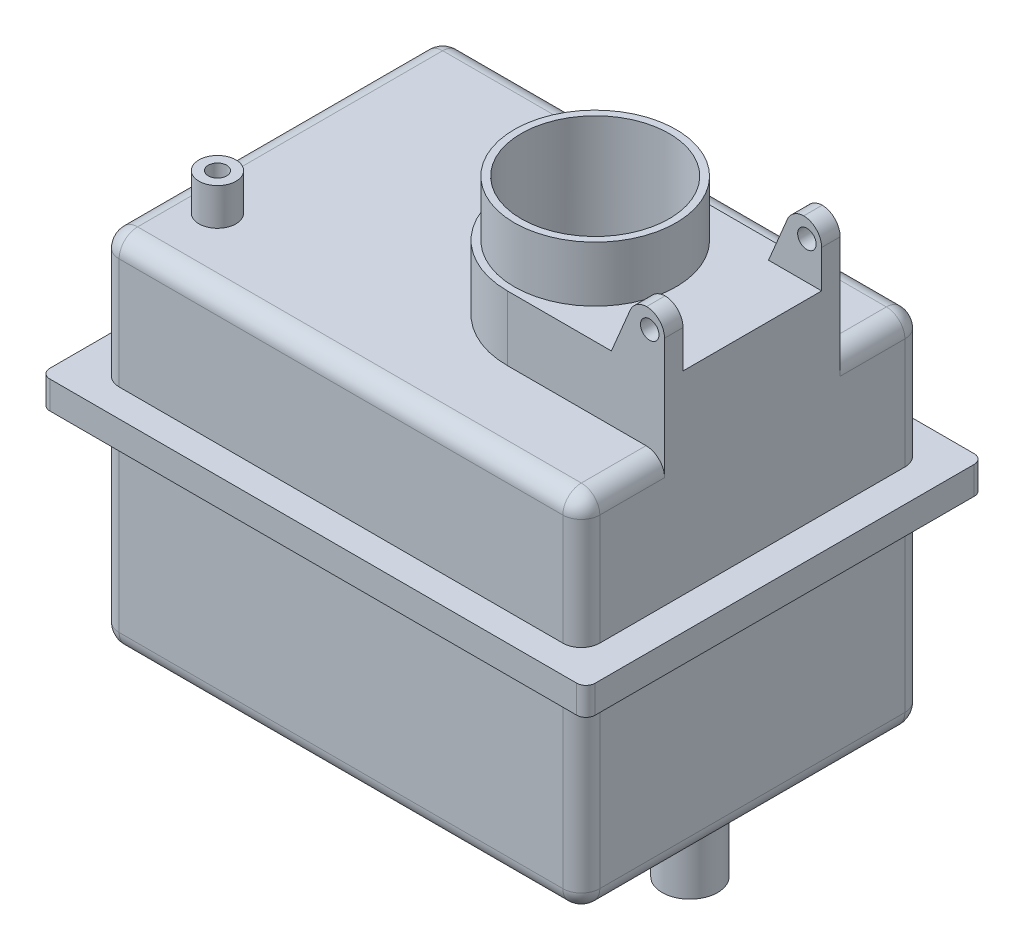
SolidWorks part; units mm, degrees
material "PBT General Purpose"
ref_plane "Front Plane" through (0, 0, 0) normal (0, 0, 1) x (1, 0, 0)
ref_plane "Top Plane" through (0, 0, 0) normal (0, 1, 0) x (1, 0, 0)
ref_plane "Right Plane" through (0, 0, 0) normal (1, 0, 0) x (0, 0, -1)
sketch "Sketch1" plane through (0, 0, 0) normal (0, 1, 0) x (1, 0, 0)
  line L1 (0, 0) -> (52, 0)
  line L2 (0, 0) -> (0, 37)
  line L3 (0, 37) -> (52, 37)
  line L4 (52, 0) -> (52, 37)
  dimension "D1" = 37
  dimension "D2" = 52
extrude "Boss-Extrude1" add sketch "Sketch1" along normal blind 22
sketch "Sketch2" plane through (0, 22, 0) normal (0, 1, 0) x (1, 0, 0)
  line L0 (26, 40) -> (26, 37) construction
  line L1 (-3.5, 40) -> (55.5, 40)
  line L2 (-3.5, 40) -> (-3.5, -3)
  line L3 (-3.5, -3) -> (55.5, -3)
  line L4 (55.5, 40) -> (55.5, -3)
  line L5 (-3.5, 40) -> (55.5, -3) construction
  line L6 (-3.5, -3) -> (55.5, 40) construction
  line L7 (52, 37) -> (0, 37) construction
  line L8 (26, 0) -> (26, -3) construction
  line L9 (0, 0) -> (52, 0) construction
  point P0 (26, 18.5)
  dimension "D1" = 59
  dimension "D2" = 43
extrude "Boss-Extrude2" add sketch "Sketch2" along normal blind 3
sketch "Sketch3" plane through (0, 25, 0) normal (0, 1, 0) x (1, 0, 0)
  line L0 (26, 37) -> (26, 40) construction
  line L1 (0, 37) -> (52, 37)
  line L2 (0, 37) -> (0, 0)
  line L3 (0, 0) -> (52, 0)
  line L4 (52, 37) -> (52, 0)
  line L5 (0, 37) -> (52, 0) construction
  line L6 (0, 0) -> (52, 37) construction
  line L7 (55.5, 40) -> (-3.5, 40) construction
  line L8 (26, 0) -> (26, -3) construction
  line L9 (-3.5, -3) -> (55.5, -3) construction
  point P0 (26, 18.5)
  dimension "D1" = 37
  dimension "D2" = 52
extrude "Boss-Extrude3" add sketch "Sketch3" along normal blind 12
sketch "Sketch4" plane through (0, 37, 0) normal (0, 1, 0) x (1, 0, 0)
  line L1 (1.3582, 35.9949) -> (50.6418, 35.9949)
  line L2 (1.3582, 35.9949) -> (1.3582, 1.0051)
  line L3 (1.3582, 1.0051) -> (50.6418, 1.0051)
  line L4 (50.6418, 35.9949) -> (50.6418, 1.0051)
  line L5 (1.3582, 35.9949) -> (50.6418, 1.0051) construction
  line L6 (1.3582, 1.0051) -> (50.6418, 35.9949) construction
  point P0 (26, 18.5)
extrude "Cut-Extrude1" cut sketch "Sketch4" against normal blind 36
sketch "Sketch5" plane through (0, 37, 0) normal (0, 1, 0) x (1, 0, 0)
  line L0 (52, 0) -> (52, 37) construction
  line L1 (0, 0) -> (52, 0)
  line L2 (0, 0) -> (0, 37)
  line L3 (0, 37) -> (52, 37)
  line L4 (52, 0) -> (52, 37)
extrude "Boss-Extrude4" add sketch "Sketch5" along normal blind 2
fillet "Fillet1" radius 2 8 edges at (0, 39, -18.5) (0, 32, -37) (26, 39, -37) (52, 32, -37) (52, 39, -18.5) (52, 32, 0) (0, 32, 0) (26, 39, 0)
fillet "Fillet2" radius 1 4 edges at (55.5, 23.5, 3) (55.5, 23.5, -40) (-3.5, 23.5, -40) (-3.5, 23.5, 3)
fillet "Fillet3" radius 2 8 edges at (52, 0, -18.5) (52, 11, -37) (26, 0, -37) (26, 0, 0) (0, 0, -18.5) (0, 11, -37) (0, 11, 0) (52, 11, 0)
sketch "Sketch6" plane through (0, 39, 0) normal (0, 1, 0) x (1, 0, 0)
  line L0 (50, 35) -> (50, 2) construction
  line L1 (52, 37) -> (52, 0) construction
  line L2 (52, 28) -> (52, 9)
  line L4 (52, 28) -> (35, 28)
  line L5 (52, 28) -> (52, 9)
  line L6 (52, 9) -> (35, 9)
  line L7 (35, 28) -> (35, 9)
  point P9 (52, 18.5)
  line M6 (50, 2) -> (50, 35)
  dimension "D1" = 19
  dimension "D2" = 17
extrude "Boss-Extrude5" add sketch "Sketch6" against normal blind 2 contours L6 L2 L4 M6 region at (51, 39, -18.5)
sketch "Sketch7" plane through (0, 39, 0) normal (0, 1, 0) x (1, 0, 0)
  line L1 (52, 9) -> (35, 9)
  line L2 (52, 9) -> (52, 28)
  line L3 (52, 28) -> (35, 28)
  line L4 (35, 9) -> (35, 28)
  dimension "D1" = 19
  dimension "D2" = 17
extrude "Boss-Extrude6" add sketch "Sketch7" along normal blind 7
sketch "Sketch8" plane through (0, 46, 0) normal (0, 1, 0) x (1, 0, 0)
  line L0 (35, 28) -> (35, 9) construction
  circle A0 centre (35, 18.5) radius 9.5
  circle A1 centre (35, 18.5) radius 8
  dimension "D1" = 19
  dimension "D2" = 16
extrude "Boss-Extrude7" add sketch "Sketch8" against normal blind 7
sketch "Sketch9" plane through (0, 46, 0) normal (0, 1, 0) x (1, 0, 0)
  line L0 (35, 26.5) -> (35, 10.5) construction
  circle A0 centre (35, 18.5) radius 8
  dimension "D1" = 16
extrude "Cut-Extrude2" cut sketch "Sketch9" against normal blind 10
sketch "Sketch10" plane through (0, 46, 0) normal (0, 1, 0) x (1, 0, 0)
  circle A0 centre (35, 18.5) radius 8.75
  circle A1 centre (35, 18.5) radius 8
  dimension "D1" = 17.5
  dimension "D2" = 16
extrude "Boss-Extrude8" add sketch "Sketch10" along normal blind 6
sketch "Sketch11" plane through (0, 0, -9) normal (0, 0, 1) x (1, 0, 0)
  line L0 (52, 46) -> (52, 52.068)
  line L1 (52, 52.068) -> (48.7989, 52.068)
  line L2 (48.7989, 52.068) -> (46.2515, 46)
  line L3 (35, 46) -> (52, 46) construction
  circle A0 centre (50.3994, 50.0726) radius 1
  line M3 (52, 46) -> (35, 46)
  dimension "D1" = 2
extrude "Boss-Extrude9" add sketch "Sketch11" against normal blind 2 contours L1 L2 L0 A0 M3 region at (49.611, 48.5726, -9)
sketch "Sketch12" plane through (0, 0, -28) normal (0, 0, -1) x (-1, 0, 0)
  line L0 (-52, 46) -> (-52, 52.068)
  line L1 (-52, 52.068) -> (-48.7989, 52.068)
  line L2 (-52, 52.068) -> (-48.7989, 52.068) construction
  line L3 (-48.7989, 52.068) -> (-46.2515, 46)
  circle A0 centre (-50.3994, 50.0726) radius 1
  line M5 (-35, 46) -> (-52, 46)
extrude "Boss-Extrude10" add sketch "Sketch12" against normal blind 2 contours L3 L1 L0 A0 M5 region at (49.611, 48.5726, -28)
fillet "Fillet4" radius 2 4 edges at (48.7989, 52.068, -27) (48.7989, 52.068, -10) (52, 52.068, -10) (52, 52.068, -27)
sketch "Sketch13" plane through (0, 39, 0) normal (0, 1, 0) x (1, 0, 0)
  circle A0 centre (5.0433, 7.5936) radius 2
  dimension "D1" = 4
extrude "Boss-Extrude11" add sketch "Sketch13" along normal blind 4
sketch "Sketch14" plane through (0, 43, 0) normal (0, 1, 0) x (1, 0, 0)
  circle A0 centre (5.0433, 7.5936) radius 1
  dimension "D1" = 2
extrude "Cut-Extrude3" cut sketch "Sketch14" against normal blind 16
sketch "Sketch15" plane through (0, 0, 0) normal (0, -1, 0) x (1, 0, 0)
  circle A0 centre (9.4357, -27.7314) radius 5
  dimension "D1" = 10
extrude "Boss-Extrude12" add sketch "Sketch15" along normal blind 6
sketch "Sketch16" plane through (0, -6, 0) normal (0, -1, 0) x (1, 0, 0)
  circle A0 centre (9.4357, -27.7314) radius 4.25
  dimension "D1" = 8.5
extrude "Cut-Extrude4" cut sketch "Sketch16" against normal blind 12
sketch "Sketch17" plane through (0, -6, 0) normal (0, -1, 0) x (1, 0, 0)
  circle A0 centre (9.4357, -27.7314) radius 5
extrude "Boss-Extrude13" add sketch "Sketch17" along normal blind 1
ref_plane "Plane1" through (4.4357, 0, 0) normal (-1, 0, 0) x (0, 0, 1)
sketch "Sketch18" plane through (4.4357, 0, 0) normal (-1, 0, 0) x (0, 0, 1)
  circle A0 centre (-27.8879, -4.2305) radius 2
  dimension "D1" = 4
extrude "Boss-Extrude14" add sketch "Sketch18" against normal blind 1
sketch "Sketch19" plane through (4.4357, 0, 0) normal (-1, 0, 0) x (0, 0, 1)
  circle A0 centre (-27.8879, -4.2305) radius 2
extrude "Boss-Extrude15" add sketch "Sketch19" along normal blind 5
sketch "Sketch20" plane through (-0.5643, 0, 0) normal (-1, 0, 0) x (0, 0, 1)
  circle A0 centre (-27.8879, -4.2305) radius 1
  dimension "D1" = 2
extrude "Cut-Extrude5" cut sketch "Sketch20" against normal blind 7
sketch "Sketch21" plane through (0, 0, 0) normal (0, -1, 0) x (1, 0, 0)
  line L0 (5.9367, -2) -> (5.9367, -35.1388) construction
  line L1 (50, -2) -> (2, -2) construction
  line L2 (45.2444, -2) -> (45.2444, -35) construction
  line L3 (2, -35) -> (50, -35) construction
  circle A0 centre (5.9367, -18.5694) radius 3
  circle A1 centre (45.2444, -18.5) radius 3
  dimension "D1" = 6
  dimension "D2" = 6
extrude "Boss-Extrude16" add sketch "Sketch21" along normal blind 8.5
sketch "Sketch22" plane through (0, -8.5, 0) normal (0, -1, 0) x (1, 0, 0)
  circle A0 centre (45.2444, -18.5) radius 1.25
  circle A1 centre (5.9367, -18.5694) radius 1.25
  dimension "D1" = 2.5
  dimension "D2" = 2.5
extrude "Cut-Extrude6" cut sketch "Sketch22" against normal blind 8
cosmetic thread "Cosmetic Thread1" parameters "D2"=3
cosmetic thread "Cosmetic Thread2" parameters "D2"=3
